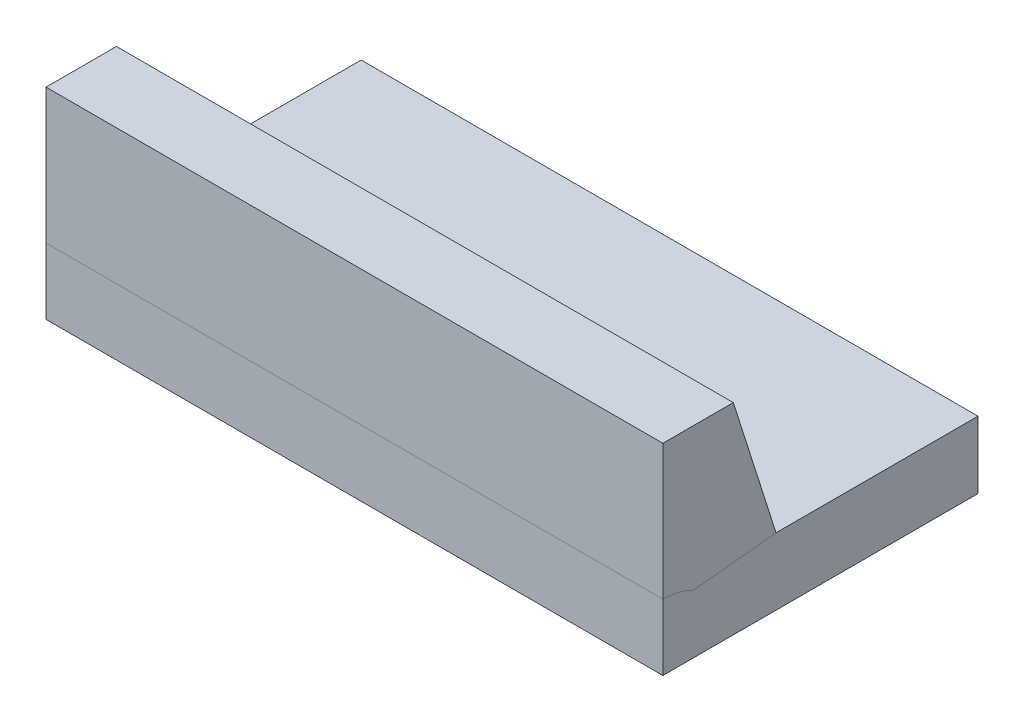
SolidWorks part; units mm, degrees
ref_plane "Front Plane" through (0, 0, 0) normal (0, 0, 1) x (1, 0, 0)
ref_plane "Top Plane" through (0, 0, 0) normal (0, 1, 0) x (1, 0, 0)
ref_plane "Right Plane" through (0, 0, 0) normal (1, 0, 0) x (0, 0, -1)
sketch "Sketch1" plane through (0, 0, 0) normal (0, 1, 0) x (1, 0, 0)
  line L1 (-23.9264, 12.7301) -> (22.0736, 12.7301)
  line L2 (-23.9264, 12.7301) -> (-23.9264, -10.7699)
  line L3 (-23.9264, -10.7699) -> (22.0736, -10.7699)
  line L4 (22.0736, 12.7301) -> (22.0736, -10.7699)
  dimension "D1" = 46
  dimension "D2" = 23.5
extrude "Boss-Extrude1" add sketch "Sketch1" along normal blind 5
sketch "Sketch2" plane through (0, 5, 0) normal (0, 1, 0) x (1, 0, 0)
  line L0 (22.0736, -10.7699) -> (22.0736, 12.7301) construction
  line L1 (22.0736, -0.332) -> (-23.9264, -0.332)
  line L2 (22.0736, -0.332) -> (22.0736, -10.7699)
  line L3 (22.0736, -10.7699) -> (-23.9264, -10.7699)
  line L4 (-23.9264, -0.332) -> (-23.9264, -10.7699)
extrude "Boss-Extrude2" add sketch "Sketch2" along normal blind 10 separate body contours L1 L4 L3 L2
extrude "Boss-Extrude3" add sketch "Sketch1<2>" along normal blind 5
sketch "Sketch1<2>" plane through (0, 0, 0) normal (0, 1, 0) x (1, 0, 0) same geometry as "Sketch1"
sketch "Sketch3" plane through (0, 0, 0) normal (0, -1, 0) x (1, 0, 0)
  circle A0 centre (17.3172, -0.322) radius 2
  circle A1 centre (-11.8074, -0.5419) radius 2
extrude "Cut-Extrude1" cut sketch "Sketch3" against normal through all both and the other way through all
sketch "Sketch4" plane through (22.0736, 0, 0) normal (1, 0, 0) x (0, 0, -1)
  circle A0 centre (-10.7699, 0) radius 4.9304
extrude "Cut-Extrude2" cut sketch "Sketch4" against normal through all both and the other way through all
sketch "Sketch5" plane through (22.0736, 0, 0) normal (1, 0, 0) x (0, 0, -1)
  line L0 (-0.332, 5) -> (-2.332, 5)
  line L1 (-2.332, 5) -> (-5.5174, 15)
  line L2 (-0.332, 15) -> (-10.7699, 15) construction
  line L3 (-5.5174, 15) -> (-0.332, 15)
  line L4 (-0.332, 15) -> (-0.332, 5)
  dimension "D1" = 2
extrude "Cut-Extrude3" cut sketch "Sketch5" against normal through all both
